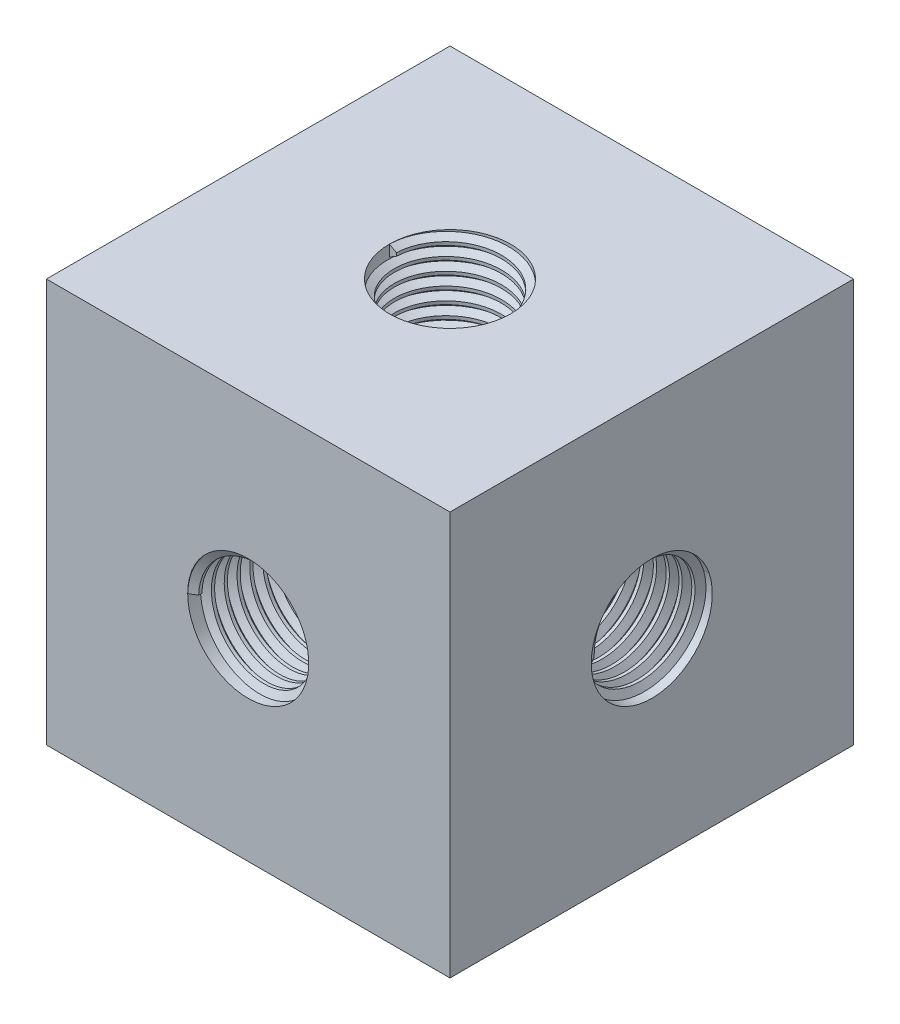
SolidWorks part; units mm, degrees
ref_plane "前视基准面" through (0, 0, 0) normal (0, 0, 1) x (1, 0, 0)
ref_plane "上视基准面" through (0, 0, 0) normal (0, 1, 0) x (1, 0, 0)
ref_plane "右视基准面" through (0, 0, 0) normal (1, 0, 0) x (0, 0, -1)
sketch "草图1" plane through (0, 0, 0) normal (0, 0, 1) x (1, 0, 0)
  line L1 (0, 0) -> (10, 0)
  line L2 (0, 0) -> (0, -10)
  line L3 (0, -10) -> (10, -10)
  line L4 (10, 0) -> (10, -10)
  circle A0 centre (5, -5) radius 1.5
  dimension "D1" = 10
  dimension "D2" = 10
extrude "凸台-拉伸1" add sketch "草图1" along normal blind 10
sketch "草图2" plane through (10, 0, 0) normal (1, 0, 0) x (0, 0, -1)
  circle A0 centre (-5, -5) radius 1.5
extrude "切除-拉伸1" cut sketch "草图2" against normal blind 10
sketch "草图3" plane through (0, 0, 0) normal (0, 1, 0) x (1, 0, 0)
  circle A0 centre (5, -5) radius 1.5
extrude "切除-拉伸2" cut sketch "草图3" against normal blind 10
thread "螺纹线1" pitch 0.3175 method extrude profile "螺纹线轮廓1" start angle 0, offset 0, length 3, pitch 0.3175, diameter 3
ref_plane "基准面1" through (3.5, 0, 5) normal (0, 0, 1) x (-1, 0, 0)
sketch "螺纹线轮廓1" plane through (3.5, 0, 5) normal (0, 0, 1) x (-1, 0, 0)
  line L0 (0, 0) -> (0, 0.3175) construction
  line L11 (0, 0) -> (0, 0.2778)
  line L12 (0, 0.2778) -> (-0.1719, 0.1786)
  line L13 (-0.1719, 0.1786) -> (-0.1719, 0.0992)
  line L15 (-0.1719, 0.0992) -> (0, 0)
  line L17 (-0.1719, 0.1389) -> (0, 0.1389) construction
  point P2 (0, 0)
  dimension "Pitch" = 0.3175
  dimension "Profile_Angle" = 60
  dimension "Profile_Land" = 0.0794
  dimension "Profile_Height" = 0.1719
thread "螺纹线2" pitch 0.3175 method extrude profile "螺纹线轮廓2" start angle 0, offset 0, length 3, pitch 0.3175, diameter 3
ref_plane "基准面2" through (6.5, -5, 0) normal (0, -1, 0) x (1, 0, 0)
sketch "螺纹线轮廓2" plane through (6.5, -5, 0) normal (0, -1, 0) x (1, 0, 0)
  line L0 (0, 0) -> (0, 0.3175) construction
  line L11 (0, 0) -> (0, 0.2778)
  line L12 (0, 0.2778) -> (-0.1719, 0.1786)
  line L13 (-0.1719, 0.1786) -> (-0.1719, 0.0992)
  line L15 (-0.1719, 0.0992) -> (0, 0)
  line L17 (-0.1719, 0.1389) -> (0, 0.1389) construction
  point P2 (0, 0)
  dimension "Pitch" = 0.3175
  dimension "Profile_Angle" = 60
  dimension "Profile_Land" = 0.0794
  dimension "Profile_Height" = 0.1719
thread "螺纹线3" pitch 0.3175 method extrude profile "螺纹线轮廓3" start angle 0, offset 0, length 3, pitch 0.3175, diameter 3
ref_plane "基准面3" through (6.5, -10, 5) normal (0, 0, 1) x (1, 0, 0)
sketch "螺纹线轮廓3" plane through (6.5, -10, 5) normal (0, 0, 1) x (1, 0, 0)
  line L0 (0, 0) -> (0, 0.3175) construction
  line L11 (0, 0) -> (0, 0.2778)
  line L12 (0, 0.2778) -> (-0.1719, 0.1786)
  line L13 (-0.1719, 0.1786) -> (-0.1719, 0.0992)
  line L15 (-0.1719, 0.0992) -> (0, 0)
  line L17 (-0.1719, 0.1389) -> (0, 0.1389) construction
  point P2 (0, 0)
  dimension "Pitch" = 0.3175
  dimension "Profile_Angle" = 60
  dimension "Profile_Land" = 0.0794
  dimension "Profile_Height" = 0.1719
thread "螺纹线4" pitch 0.3175 method extrude profile "螺纹线轮廓4" start angle 0, offset 0, length 3, pitch 0.3175, diameter 3
ref_plane "基准面4" through (10, -5, 6.5) normal (0, -1, 0) x (0, 0, 1)
sketch "螺纹线轮廓4" plane through (10, -5, 6.5) normal (0, -1, 0) x (0, 0, 1)
  line L0 (0, 0) -> (0, 0.3175) construction
  line L11 (0, 0) -> (0, 0.2778)
  line L12 (0, 0.2778) -> (-0.1719, 0.1786)
  line L13 (-0.1719, 0.1786) -> (-0.1719, 0.0992)
  line L15 (-0.1719, 0.0992) -> (0, 0)
  line L17 (-0.1719, 0.1389) -> (0, 0.1389) construction
  point P2 (0, 0)
  dimension "Pitch" = 0.3175
  dimension "Profile_Angle" = 60
  dimension "Profile_Land" = 0.0794
  dimension "Profile_Height" = 0.1719
thread "螺纹线5" pitch 0.3175 method extrude profile "螺纹线轮廓5" start angle 0, offset 0, length 3, pitch 0.3175, diameter 3
ref_plane "基准面5" through (0, -5, 3.5) normal (0, -1, 0) x (0, 0, -1)
sketch "螺纹线轮廓5" plane through (0, -5, 3.5) normal (0, -1, 0) x (0, 0, -1)
  line L0 (0, 0) -> (0, 0.3175) construction
  line L11 (0, 0) -> (0, 0.2778)
  line L12 (0, 0.2778) -> (-0.1719, 0.1786)
  line L13 (-0.1719, 0.1786) -> (-0.1719, 0.0992)
  line L15 (-0.1719, 0.0992) -> (0, 0)
  line L17 (-0.1719, 0.1389) -> (0, 0.1389) construction
  point P2 (0, 0)
  dimension "Pitch" = 0.3175
  dimension "Profile_Angle" = 60
  dimension "Profile_Land" = 0.0794
  dimension "Profile_Height" = 0.1719
thread "螺纹线6" pitch 0.3175 method extrude profile "螺纹线轮廓6" start angle 0, offset 0, length 3, pitch 0.3175, diameter 3
ref_plane "基准面6" through (3.5, -5, 10) normal (0, -1, 0) x (-1, 0, 0)
sketch "螺纹线轮廓6" plane through (3.5, -5, 10) normal (0, -1, 0) x (-1, 0, 0)
  line L0 (0, 0) -> (0, 0.3175) construction
  line L11 (0, 0) -> (0, 0.2778)
  line L12 (0, 0.2778) -> (-0.1719, 0.1786)
  line L13 (-0.1719, 0.1786) -> (-0.1719, 0.0992)
  line L15 (-0.1719, 0.0992) -> (0, 0)
  line L17 (-0.1719, 0.1389) -> (0, 0.1389) construction
  point P2 (0, 0)
  dimension "Pitch" = 0.3175
  dimension "Profile_Angle" = 60
  dimension "Profile_Land" = 0.0794
  dimension "Profile_Height" = 0.1719
